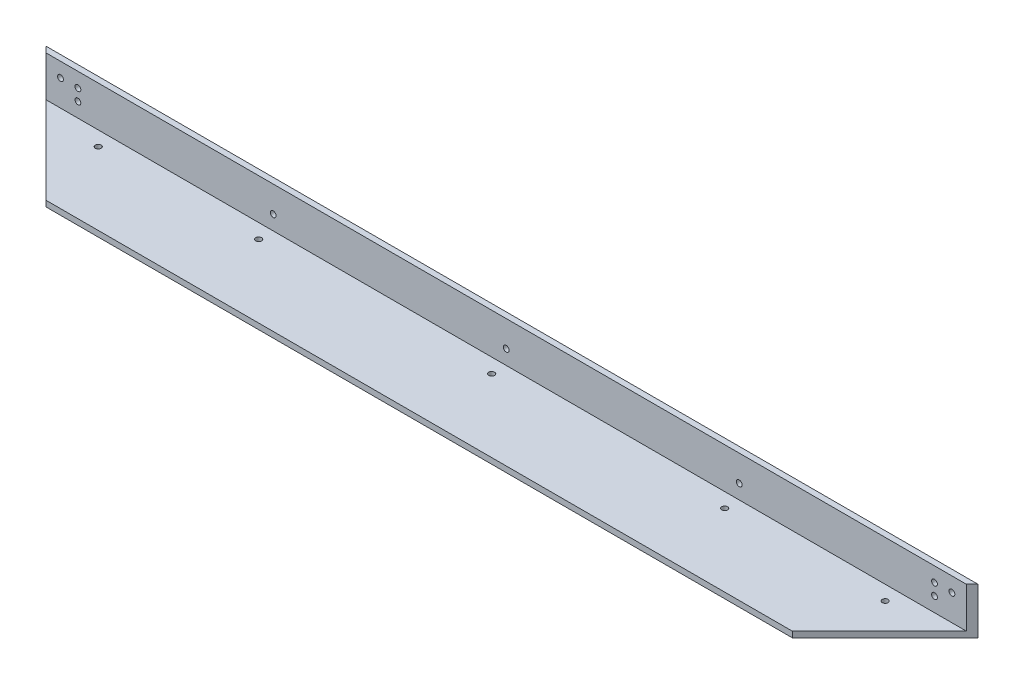
SolidWorks part; units mm, degrees
ref_plane "Front Plane" through (0, 0, 0) normal (0, 0, 1) x (1, 0, 0)
ref_plane "Top Plane" through (0, 0, 0) normal (0, 1, 0) x (1, 0, 0)
ref_plane "Right Plane" through (0, 0, 0) normal (1, 0, 0) x (0, 0, -1)
sketch "Sketch1" plane through (0, 0, 0) normal (1, 0, 0) x (0, 0, -1)
  line L0 (0, 0) -> (-50.8, 0)
  line L1 (-50.8, 0) -> (-50.8, 3.175)
  line L2 (-50.8, 3.175) -> (-3.175, 3.175)
  line L3 (-3.175, 3.175) -> (-3.175, 25.4)
  line L4 (-3.175, 25.4) -> (0, 25.4)
  line L5 (0, 25.4) -> (0, 0)
  dimension "LHeight" = 25.4
  dimension "LWidth" = 50.8
  dimension "LMaterialThickness" = 3.175
  dimension "D1" = 47.625
  dimension "D2" = 22.225
  dimension "D3" = 3.175
extrude "Boss-Extrude1" add sketch "Sketch1" along normal blind 510
chamfer "Chamfer6" distance 50.8 angle 45 1 edges at (510, 1.5875, 50.8)
chamfer "Chamfer7" distance 50.8 angle 45 1 edges at (0, 1.5875, 50.8)
sketch "FrontSideHoles-Sketch2" plane through (0, 0, 0) normal (0, 0, -1) x (-1, 0, 0)
  line L0 (0, 0) -> (0, 25.4) construction
  line L1 (-510, 0) -> (0, 0) construction
  line L2 (-510, 0) -> (-510, 25.4) construction
  circle A0 centre (-498.8875, 17.4625) radius 1.5875
  circle A1 centre (-489.3625, 17.4625) radius 1.5875
  circle A2 centre (-20.6375, 17.4625) radius 1.5875
  circle A3 centre (-11.1125, 17.4625) radius 1.5875
  circle A5 centre (-20.6375, 11.1125) radius 1.5875
  circle A6 centre (-489.3625, 11.1125) radius 1.5875
  circle A8 centre (-382.5, 11.1125) radius 1.5875
  circle A9 centre (-255, 11.1125) radius 1.5875
  circle A10 centre (-127.5, 11.1125) radius 1.5875
  dimension "D5" = 3.175
  dimension "D1" = 11.1125
  dimension "D2" = 20.6375
  dimension "D3" = 11.1125
  dimension "D4" = 20.6375
  dimension "D6" = 7.9375
  dimension "D8" = 127.5
  dimension "D9" = 127.5
  dimension "D10" = 127.5
  dimension "D7" = 11.1125
extrude "FrontSideHoles-Cut-Extrude2" cut sketch "FrontSideHoles-Sketch2" against normal through all
sketch "BottomHoles-Sketch2" plane through (0, 0, 0) normal (0, -1, 0) x (1, 0, 0)
  line L0 (510, 0) -> (0, 0) construction
  circle A0 centre (39.6875, 11.1125) radius 1.5875
  circle A1 centre (470.3125, 11.1125) radius 1.5875
  circle A2 centre (127.5, 11.1125) radius 1.5875
  circle A3 centre (255, 11.1125) radius 1.5875
  circle A4 centre (382.5, 11.1125) radius 1.5875
  dimension "D1" = 11.1125
  dimension "D4" = 3.175
  dimension "D2" = 39.6875
  dimension "D3" = 39.6875
  dimension "D5" = 127.5
  dimension "D6" = 127.5
  dimension "D7" = 127.5
extrude "BottomHoles-Cut-Extrude1" cut sketch "BottomHoles-Sketch2" against normal through all
equation "\"LowerRailWidth\"= 2.00in"
equation "\"LowerRailHeight\"= 1.00in"
equation "\"RailThickness\"= .125in'Spec"
equation "\"SideRailHoleX1FromSide\"= \"HoleOffsetFromSide\""
equation "\"SideRailHoleX2FromSide\"= \"VSWidth\" - \"HoleOffsetFromEdge\" - \"RailThickness\"'Equals 20.6375"
equation "\"SideRailHoleY1FromEdge\"= \"HoleOffsetFromEdge\""
equation "\"FrontBackRailLength\"= 510mm"
equation "\"VSWidth\"= 1.25in'Spec"
equation "\"HoleOffsetFromEdge\"= \"RailThickness\" * 2.5"
equation "\"HoleOffsetFromSide\"= \"RailThickness\" * 3.5"
equation "\"SideRailHoleY2FromSide\"= \"HoleOffsetFromSide\""
equation "\"FasteningHoleDiameter\"= .125in"
equation "\"D1@Boss-Extrude1\"=\"FrontBackRailLength\""
equation "\"D1@Chamfer6\"=\"LowerRailWidth\""
equation "\"D1@Chamfer7\"=\"LowerRailWidth\""
equation "\"D1@FrontSideHoles-Sketch2\" = \"SideRailHoleX1FromSide\""
equation "\"D2@FrontSideHoles-Sketch2\" = \"SideRailHoleX2FromSide\""
equation "\"D3@FrontSideHoles-Sketch2\" = \"SideRailHoleX1FromSide\""
equation "\"D4@FrontSideHoles-Sketch2\" = \"SideRailHoleX2FromSide\""
equation "\"D5@FrontSideHoles-Sketch2\" = \"FasteningHoleDiameter\""
equation "\"D6@FrontSideHoles-Sketch2\" = \"SideRailHoleY1FromEdge\""
equation "\"LHeight@Sketch1\"=\"LowerRailHeight\""
equation "\"LWidth@Sketch1\"=\"LowerRailWidth\""
equation "\"LowerCornerBlockWidth\"= \"LowerRailWidth\" - \"RailThickness\" * 2'Room for left front stepper"
equation "\"D1@BottomHoles-Sketch2\"=\"LowerCornerBlockY1FromSide\""
equation "\"D2@BottomHoles-Sketch2\"=\"CornerEnclosureOffset\""
equation "\"D3@BottomHoles-Sketch2\"=\"CornerEnclosureOffset\""
equation "\"D4@BottomHoles-Sketch2\" = \"FasteningHoleDiameter\""
equation "\"CornerEnclosureOffset\"= \"LowerCornerBlockWidth\" - \"HoleOffsetFromEdge\" + \"RailThickness\""
equation "\"LowerCornerBlockY1FromSide\"= \"HoleOffsetFromSide\""
equation "\"FrontOrBackEnclosureOffsets\"= \"FrontBackRailLength\" / 4"
equation "\"D5@BottomHoles-Sketch2\"=\"FrontOrBackEnclosureOffsets\""
equation "\"D6@BottomHoles-Sketch2\"=\"FrontOrBackEnclosureOffsets\""
equation "\"D7@BottomHoles-Sketch2\"=\"FrontOrBackEnclosureOffsets\""
equation "\"D8@FrontSideHoles-Sketch2\"=\"FrontOrBackEnclosureOffsets\""
equation "\"D9@FrontSideHoles-Sketch2\"=\"FrontOrBackEnclosureOffsets\""
equation "\"D10@FrontSideHoles-Sketch2\"=\"FrontOrBackEnclosureOffsets\""
equation "\"D7@FrontSideHoles-Sketch2\"=\"SideRailHoleY2FromSide\""
